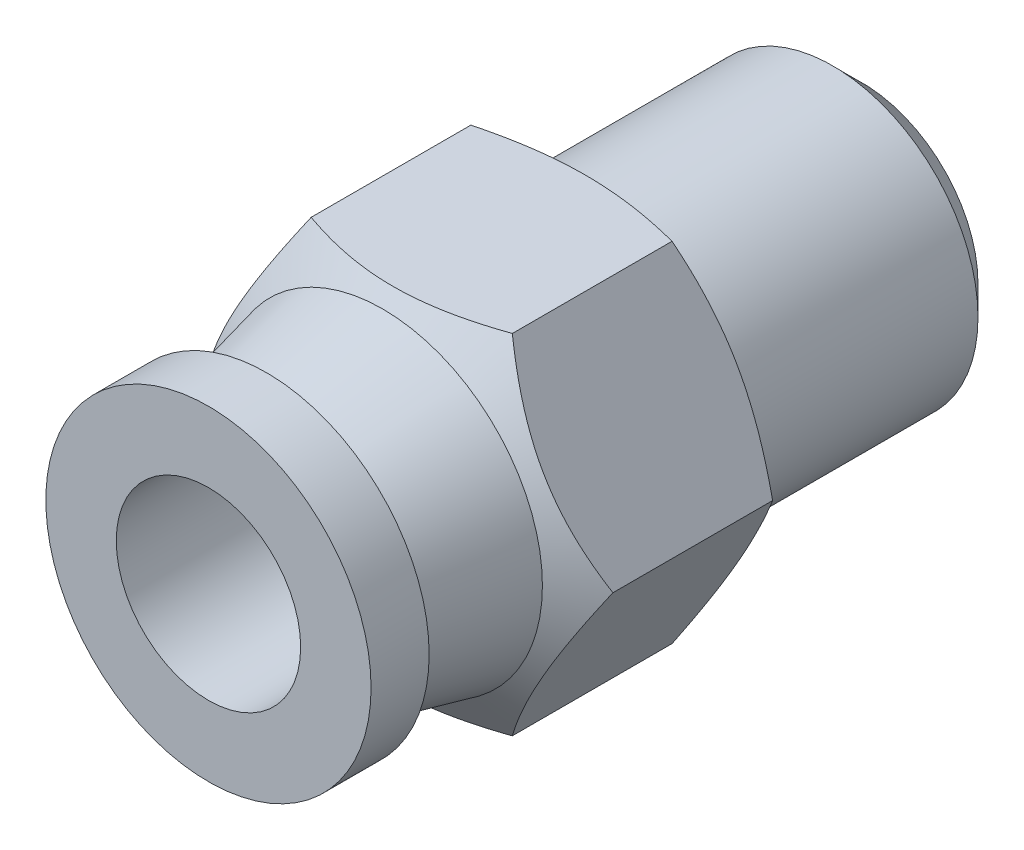
SolidWorks part; units mm, degrees
material "Brass"
ref_plane "Front Plane" through (0, 0, 0) normal (0, 0, 1) x (1, 0, 0)
ref_plane "Top Plane" through (0, 0, 0) normal (0, 1, 0) x (1, 0, 0)
ref_plane "Right Plane" through (0, 0, 0) normal (1, 0, 0) x (0, 0, -1)
sketch "Sketch1" plane through (0, 0, 0) normal (0, 0, 1) x (1, 0, 0)
  circle A0 centre (0, 0) radius 5
  dimension "D1" = 10
extrude "Boss-Extrude1" add sketch "Sketch1" along normal blind 9
sketch "Sketch2" plane through (0, 0, 9) normal (0, 0, 1) x (1, 0, 0)
  line L1 (6.9282, 0) -> (3.4641, 6)
  line L2 (3.4641, 6) -> (-3.4641, 6)
  line L3 (-3.4641, 6) -> (-6.9282, 0)
  line L4 (-6.9282, 0) -> (-3.4641, -6)
  line L5 (-3.4641, -6) -> (3.4641, -6)
  line L6 (3.4641, -6) -> (6.9282, 0)
  circle A0 centre (0, 0) radius 6 construction
  dimension "D1" = 12
extrude "Boss-Extrude2" add sketch "Sketch2" along normal blind 7.5
sketch "Sketch3" plane through (0, 0, 16.5) normal (0, 0, 1) x (1, 0, 0)
  circle A0 centre (0, 0) radius 5.5
  dimension "D1" = 11
extrude "Boss-Extrude3" add sketch "Sketch3" along normal blind 4 draft 13
sketch "Sketch4" plane through (0, 0, 20.5) normal (0, 0, 1) x (1, 0, 0)
  circle A0 centre (0, 0) radius 5.6
  dimension "D1" = 11.2
extrude "Boss-Extrude4" add sketch "Sketch4" along normal blind 2
sketch "Sketch5" plane through (0, 0, 22.5) normal (0, 0, 1) x (1, 0, 0)
  circle A0 centre (0, 0) radius 3.175
  dimension "D1" = 6.35
extrude "Cut-Extrude1" cut sketch "Sketch5" against normal blind 13
sketch "Sketch6" plane through (0, 0, 0) normal (0, 0, -1) x (-1, 0, 0)
  circle A0 centre (0, 0) radius 2
  dimension "D1" = 4
extrude "Cut-Extrude2" cut sketch "Sketch6" against normal through all
ref_axis "Longitudinal Axis" through (0, 0, -1.125) along (0, 0, 1)
sketch "Sketch7" plane through (0, 0, 0) normal (0, 1, 0) x (1, 0, 0)
  line L0 (5, -9) -> (6.9282, -10)
  line L1 (6.9282, -16.5) -> (6.9282, -9) construction
  line L2 (6.9282, -10) -> (6.9282, -9)
  line L3 (6.9282, -9) -> (5, -9)
  line L4 (6.9282, -12.75) -> (-6.9282, -12.75) construction
  line L5 (-6.9282, -16.5) -> (-6.9282, -9) construction
  line L6 (6.9282, -15.5) -> (6.9282, -16.5)
  line L7 (6.9282, -16.5) -> (5.5, -16.5)
  line L8 (5.5, -16.5) -> (6.9282, -15.5)
  line L9 (6.9282, -16.5) -> (3.4641, -16.5) construction
  line L10 (4.5765, -20.5) -> (5.5, -16.5) construction
  dimension "D1" = 1
revolve "Cut-Revolve1" cut sketch "Sketch7" angle 360 about axis through (0, 0, -1.125) along (0, 0, 1)
chamfer "Chamfer1" distance 1 angle 45 1 edges at (5, 0, 0)
chamfer "Chamfer2" distance 0.5 angle 45 1 edges at (-2, 0, 0)
ref_plane "Plane1" through (0, 0, 9) normal (0, 0, 1) x (1, 0, 0)
ref_plane "Thread insertion extent" through (0, 0, 4.5) normal (0, 0, 1) x (1, 0, 0)
other "CPoint1" parameters "Diameter"=6.35, "StubLength"=0
ref_axis "Axis2" through (0, 0, 32.5) along (0, 0, -1)
